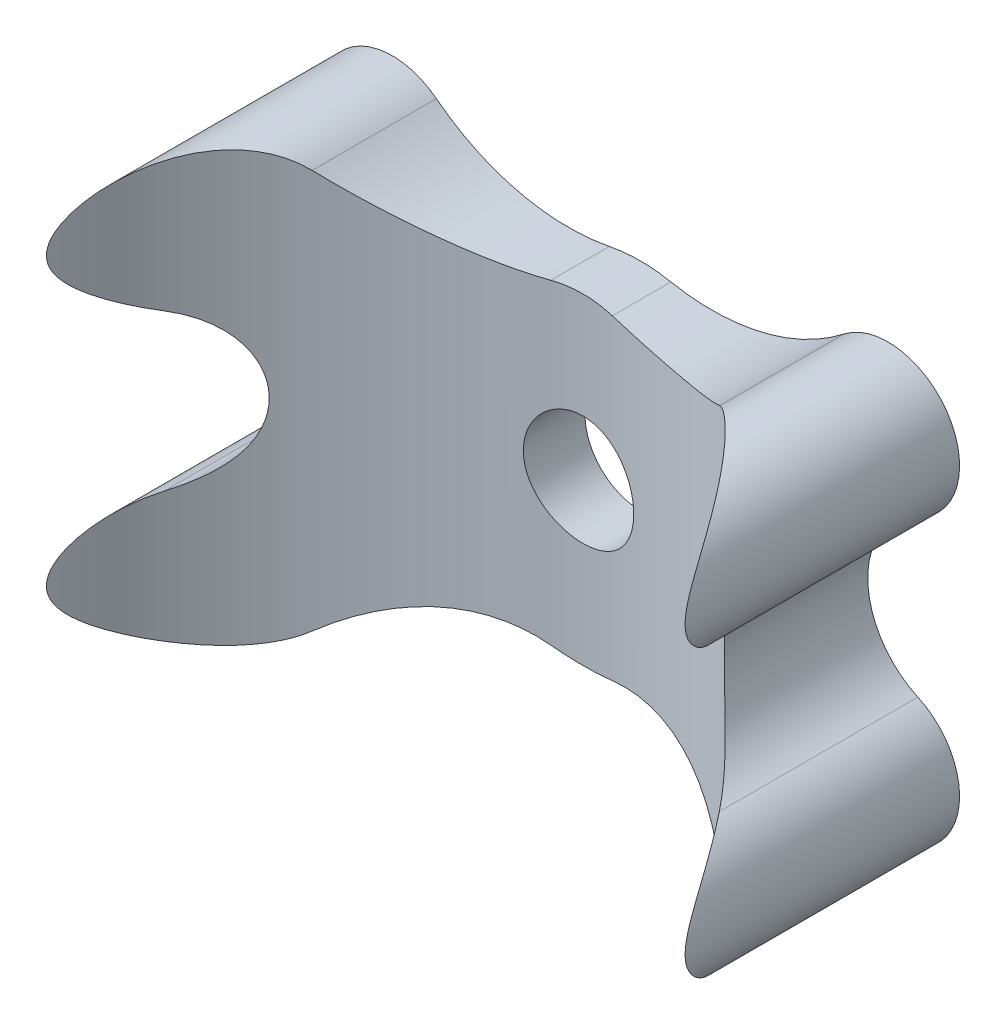
SolidWorks part; units mm, degrees
ref_plane "Front Plane" through (0, 0, 0) normal (0, 0, 1) x (1, 0, 0)
ref_plane "Top Plane" through (0, 0, 0) normal (0, 1, 0) x (1, 0, 0)
ref_plane "Right Plane" through (0, 0, 0) normal (1, 0, 0) x (0, 0, -1)
sketch "Sketch2" plane through (0, 0, 0) normal (1, 0, 0) x (0, 0, -1)
  line L5 (0, -76.2) -> (30.48, -76.2)
  line L6 (0, -76.2) -> (0, 76.2)
  line L7 (0, 76.2) -> (30.48, 76.2)
  line L8 (30.48, -76.2) -> (30.48, 76.2)
revolve "Revolve1" add sketch "Sketch2" angle 360 about L6
ref_plane "Plane1" through (0, 0, -30.48) normal (0, 0, -1) x (-1, 0, 0)
sketch "Sketch4" plane through (0, 0, -30.48) normal (0, 0, 1) x (-1, 0, 0)
  line L0 (0, 0) -> (-21.997, 12.7) construction
  line L1 (0, 0) -> (0, -14.2875) construction
  line L2 (0, 0) -> (21.997, 12.7) construction
  line L3 (-20.1969, 0) -> (20.1969, 0) construction
  arc A0 (-24.6424, -6.9273) -> (-24.6424, 6.9273) centre (-27.8169, 0) ccw
  arc A3 (24.6424, 6.9273) -> (18.0901, 17.7058) centre (21.997, 12.7) ccw
  arc A4 (2.7297, 14.0243) -> (18.0901, 17.7058) centre (6.3694, 32.7234) ccw
  arc A6 (24.6424, -6.9273) -> (18.0901, -17.7058) centre (21.997, -12.7) cw
  arc A7 (2.7297, -14.0243) -> (18.0901, -17.7058) centre (6.3694, -32.7234) cw
  arc A8 (24.6424, -6.9273) -> (24.6424, 6.9273) centre (27.8169, 0) cw
  circle A9 centre (0, 0) radius 4.8997
  arc A10 (-2.7297, -14.0243) -> (-18.0901, -17.7058) centre (-6.3694, -32.7234) ccw
  arc A11 (-24.6424, -6.9273) -> (-18.0901, -17.7058) centre (-21.997, -12.7) ccw
  arc A13 (-2.7297, 14.0243) -> (-18.0901, 17.7058) centre (-6.3694, 32.7234) cw
  arc A14 (-24.6424, 6.9273) -> (-18.0901, 17.7058) centre (-21.997, 12.7) cw
  arc A16 (2.7297, 14.0243) -> (-2.7297, 14.0243) centre (0, 0) ccw
  arc A17 (-2.7297, -14.0243) -> (2.7297, -14.0243) centre (0, 0) ccw
  point P3 (0, 0)
  point P6 (21.997, 10.16)
  point P11 (-0.0011, 0)
  point P35 (-21.997, 10.16)
  dimension "D4" = 12.7
  dimension "D6" = 7.62
  dimension "D2" = 19.05
  dimension "D3" = 30
  dimension "D7" = 10.16
extrude "Boss-Extrude1" add sketch "Sketch4" along normal blind 25.4 and the other way blind 5.08 separate body
sketch "Sketch8" plane through (0, 0, -35.56) normal (0, 0, -1) x (1, 0, 0)
  circle A2 centre (21.997, 12.7) radius 2.54
  circle A5 centre (21.997, -12.7) radius 2.54
  circle A12 centre (-21.997, -12.7) radius 2.54
  circle A15 centre (-21.997, 12.7) radius 2.54
  point P5 (21.997, 12.7)
  point P13 (21.997, -12.7)
  point P22 (-21.997, 12.7)
  point P29 (-21.997, -12.7)
  dimension "D1" = 5.08
hole_wizard "Ø5.0mm Dowel Hole1" positions "Sketch8" profile "Sketch10" hole size "Ø5.0" standard "ANSI Metric"
sketch "Sketch10" plane through (-21.997, 12.7, -35.56) normal (1, 0, 0) x (0, 1, 0)
  line L0 (0, 0) -> (0, 6.5822)
  line L1 (0, 6.5822) -> (2.5, 5.08)
  line L2 (2.5, 5.08) -> (2.5, 0)
  line L5 (2.5, 0) -> (0, 0)
  line L10 (0, 6.5822) -> (-2.5, 5.08) construction
  line L11 (0, -6.35) -> (0, 107.95) construction
  dimension "Hole Dia." = 5
  dimension "Hole Depth" = 5.08
  dimension "Drill Angle" = 118
combine bodies "Combine4" operation type subtract main body 107 bodies to subtract 101
